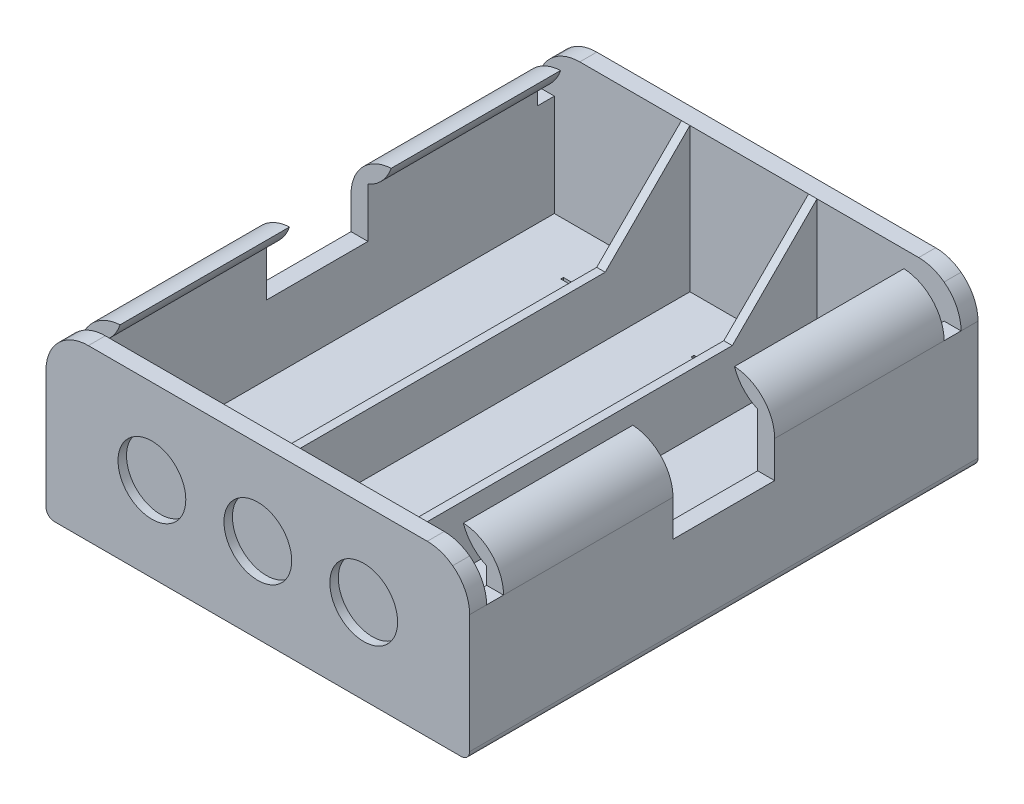
SolidWorks part; units mm, degrees
ref_plane "Plan de face" through (0, 0, 0) normal (0, 0, 1) x (1, 0, 0)
ref_plane "Plan de dessus" through (0, 0, 0) normal (0, 1, 0) x (1, 0, 0)
ref_plane "Plan de droite" through (0, 0, 0) normal (1, 0, 0) x (0, 0, -1)
sketch "Esquisse1" plane through (0, 0, 0) normal (0, 0, 1) x (1, 0, 0)
  line L1 (0, 0) -> (-50, 0)
  line L2 (0, 0) -> (0, 17)
  line L3 (0, 17) -> (-50, 17)
  line L4 (-50, 0) -> (-50, 17)
  dimension "D1" = 50
  dimension "D2" = 17
extrude "Boss.-Extru.1" add sketch "Esquisse1" along normal blind 60
sketch "Esquisse2" plane through (0, 17, 0) normal (0, 1, 0) x (1, 0, 0)
  line L0 (0, -60) -> (-50, -60) construction
  line L1 (-2, -58) -> (-48, -58)
  line L2 (-2, -58) -> (-2, -2)
  line L3 (-2, -2) -> (-48, -2)
  line L4 (-48, -58) -> (-48, -2)
  line L5 (-50, -60) -> (-50, 0) construction
  line L6 (0, -60) -> (0, 0) construction
  line L7 (0, 0) -> (-50, 0) construction
  dimension "D1" = 2
  dimension "D2" = 2
  dimension "D3" = 2
  dimension "D4" = 2
extrude "Enlèv. mat.-Extru.1" cut sketch "Esquisse2" against normal blind 14
sketch "Esquisse3" plane through (0, 17, 0) normal (0, 1, 0) x (1, 0, 0)
  line L0 (0, 0) -> (-50, 0) construction
  line L1 (0, -60) -> (-5, -60)
  line L2 (0, -60) -> (0, 0)
  line L3 (0, 0) -> (-5, 0)
  line L4 (-5, -60) -> (-5, 0)
  line L6 (-50, -60) -> (-45, -60)
  line L7 (-50, -60) -> (-50, 0)
  line L8 (-50, 0) -> (-45, 0)
  line L9 (-45, -60) -> (-45, 0)
  dimension "D1" = 5
  dimension "D2" = 5
extrude "Boss.-Extru.2" add sketch "Esquisse3" along normal blind 3
fillet "Congé4" radius 5 2 edges at (-50, 20, 30) (0, 20, 30)
fillet "Congé5" radius 5 2 edges at (-45, 17, 30) (-5, 17, 30)
sketch "Esquisse4" plane through (0, 0, 0) normal (1, 0, 0) x (0, 0, -1)
  line L0 (-30, 0) -> (-30, 21.3993)
  line L1 (-60, 0) -> (0, 0) construction
  line L3 (-30, 10.6996) -> (-36, 10.6996)
  line L4 (-30, 10.6996) -> (-30, 21.3993)
  line L5 (-30, 21.3993) -> (-36, 21.3993)
  line L6 (-36, 10.6996) -> (-36, 21.3993)
  line L7 (-30, 10.6996) -> (-24, 10.6996)
  line L8 (-30, 10.6996) -> (-30, 21.3993)
  line L9 (-30, 21.3993) -> (-24, 21.3993)
  line L10 (-24, 10.6996) -> (-24, 21.3993)
  line M4 (0, 15) -> (-60, 15)
  dimension "D1" = 6
  dimension "D2" = 6
extrude "Enlèv. mat.-Extru.2" cut sketch "Esquisse4" against normal blind 13 contours L10 L9 L0 M4 | L7 L10 L0 M4 | L6 L3 L0 M4 | L6 L0 L5 M4
sketch "Esquisse5" plane through (-50, 0, 0) normal (-1, 0, 0) x (0, 0, 1)
  line L0 (30, 0) -> (30, 22.2931)
  line L1 (60, 0) -> (0, 0) construction
  line L3 (30, 11.1466) -> (24, 11.1466)
  line L4 (30, 11.1466) -> (30, 21.3972)
  line L5 (30, 21.3972) -> (24, 21.3972)
  line L6 (24, 11.1466) -> (24, 21.3972)
  line L7 (30, 11.1466) -> (36, 11.1466)
  line L8 (30, 11.1466) -> (30, 21.3972)
  line L9 (30, 21.3972) -> (36, 21.3972)
  line L10 (36, 11.1466) -> (36, 21.3972)
  line M4 (60, 15) -> (0, 15)
  dimension "D1" = 6
  dimension "D2" = 6
extrude "Enlèv. mat.-Extru.3" cut sketch "Esquisse5" against normal blind 13 contours L6 L3 L0 M4 | L7 L10 L0 M4 | L10 L9 L0 M4 | L6 L0 L5 M4
sketch "Esquisse6" plane through (0, 17, 0) normal (0, 1, 0) x (1, 0, 0)
  line L1 (-2, 0) -> (-48, 0)
  line L2 (-2, 0) -> (-2, -2)
  line L3 (-2, -2) -> (-48, -2)
  line L4 (-48, 0) -> (-48, -2)
  line L5 (-48, -60) -> (-2, -60)
  line L6 (-48, -60) -> (-48, -58)
  line L7 (-48, -58) -> (-2, -58)
  line L8 (-2, -60) -> (-2, -58)
extrude "Boss.-Extru.3" add sketch "Esquisse6" along normal blind 3
fillet "Congé6" radius 5 1 edges at (-2, 20, 1)
fillet "Congé7" radius 5 1 edges at (-48, 20, 1)
fillet "Congé8" radius 5 2 edges at (-2, 20, 59) (-48, 20, 59)
sketch "Esquisse7" plane through (-50, 0, 0) normal (-1, 0, 0) x (0, 0, 1)
  line L0 (0, 0) -> (4, 0)
  line L1 (60, 0) -> (0, 0) construction
  line L2 (24, 15) -> (0, 15) construction
  line L3 (4, 0) -> (2, 0)
  line L4 (4, 0) -> (4, 20.2103)
  line L5 (4, 20.2103) -> (2, 20.2103)
  line L6 (2, 0) -> (2, 20.2103)
  line L7 (2, 20.2103) -> (4, 20.2103)
  line L8 (2, 20.2103) -> (2, 15)
  line L9 (2, 15) -> (4, 15)
  line L10 (4, 20.2103) -> (4, 15)
  line M4 (24, 15) -> (0, 15)
  dimension "D1" = 4
  dimension "D2" = 2
extrude "Enlèv. mat.-Extru.4" cut sketch "Esquisse7" against normal blind 62 contours L6 L4 L5 M4
sketch "Esquisse8" plane through (-50, 0, 0) normal (-1, 0, 0) x (0, 0, 1)
  line L0 (60, 0) -> (56, 0)
  line L1 (60, 0) -> (0, 0) construction
  line L2 (60, 15) -> (36, 15) construction
  line L3 (56, 0) -> (58, 0)
  line L4 (56, 0) -> (56, 23.2572)
  line L5 (56, 23.2572) -> (58, 23.2572)
  line L6 (58, 0) -> (58, 23.2572)
  line L7 (56, 23.2572) -> (58, 23.2572)
  line L8 (56, 23.2572) -> (56, 15)
  line L9 (56, 15) -> (58, 15)
  line L10 (58, 23.2572) -> (58, 15)
  line M10 (60, 15) -> (36, 15)
  dimension "D1" = 4
  dimension "D2" = 2
extrude "Enlèv. mat.-Extru.5" cut sketch "Esquisse8" against normal blind 62 contours L6 L5 L4 M10
sketch "Esquisse9" plane through (0, 3, 0) normal (0, 1, 0) x (1, 0, 0)
  line L0 (-2, -58) -> (-17, -58)
  line L1 (-48, -58) -> (-2, -58) construction
  line L2 (-48, -58) -> (-33, -58)
  line L3 (-17, -58) -> (-33, -58)
  line L4 (-2, -2) -> (-48, -2) construction
  line L5 (-17, -58) -> (-18, -58)
  line L6 (-17, -58) -> (-17, -2)
  line L7 (-17, -2) -> (-18, -2)
  line L8 (-18, -58) -> (-18, -2)
  line L10 (-33, -58) -> (-32, -58)
  line L11 (-33, -58) -> (-33, -2)
  line L12 (-33, -2) -> (-32, -2)
  line L13 (-32, -58) -> (-32, -2)
  dimension "D1" = 15
  dimension "D2" = 15
  dimension "D3" = 1
  dimension "D4" = 1
extrude "Boss.-Extru.4" add sketch "Esquisse9" along normal blind 7 contours L10 L13 L12 L11 | L5 L8 L7 L6
sketch "Esquisse13" plane through (-17, 0, 0) normal (1, 0, 0) x (0, 0, -1)
  line L0 (-58, 10) -> (-48, 10)
  line L1 (-58, 10) -> (-2, 10) construction
  line L2 (-48, 10) -> (-58, 20)
  line L3 (-58, 10) -> (-58, 20)
  dimension "D1" = 10
extrude "Boss.-Extru.5" add sketch "Esquisse13" against normal blind 1
sketch "Esquisse15" plane through (-32, 0, 0) normal (1, 0, 0) x (0, 0, -1)
  line L0 (-58, 10) -> (-48, 10)
  line L1 (-58, 10) -> (-2, 10) construction
  line L2 (-48, 10) -> (-58, 20)
  line L3 (-58, 20) -> (-58, 10)
  dimension "D1" = 10
extrude "Boss.-Extru.6" add sketch "Esquisse15" against normal blind 1
sketch "Esquisse16" plane through (-32, 0, 0) normal (1, 0, 0) x (0, 0, -1)
  line L0 (-2, 10) -> (-12.0005, 10)
  line L1 (-48, 10) -> (-2, 10) construction
  line L2 (-12.0005, 10) -> (-2, 20.0005)
  line L3 (-2, 20.0005) -> (-2, 10)
extrude "Boss.-Extru.7" add sketch "Esquisse16" against normal blind 1
sketch "Esquisse17" plane through (-17, 0, 0) normal (1, 0, 0) x (0, 0, -1)
  line L0 (-2, 10) -> (-12, 10)
  line L1 (-48, 10) -> (-2, 10) construction
  line L2 (-12, 10) -> (-2, 20)
  line L3 (-2, 20) -> (-2, 10)
  dimension "D1" = 10
extrude "Boss.-Extru.8" add sketch "Esquisse17" against normal blind 1
sketch "Esquisse18" plane through (0, 3, 0) normal (0, 1, 0) x (1, 0, 0)
  text T0 "+\r\n"
  text T1 "+"
  text T2 "+\r\n"
extrude "Enlèv. mat.-Extru.6" cut sketch "Esquisse18" against normal blind 0.5
sketch "Esquisse19" plane through (0, 3, 0) normal (0, 1, 0) x (1, 0, 0)
  text T0 "-\r\n"
  text T1 "-\r\n"
  text T2 "-\r\n"
extrude "Enlèv. mat.-Extru.7" cut sketch "Esquisse19" against normal blind 0.5
fillet "Congé9" radius 1 1 edges at (0, 0, 30)
fillet "Congé10" radius 1 1 edges at (-50, 0, 30)
sketch "Esquisse20" plane through (0, 0, 0) normal (0, 0, -1) x (-1, 0, 0)
  line L0 (0, 0) -> (50, 0)
  line L1 (25, 0) -> (0, 0)
  line L2 (25, 0) -> (50, 0)
  line L3 (12.5, 0) -> (12.5, 20)
  line L4 (5, 20) -> (45, 20) construction
  line L5 (25, 0) -> (25, 20)
  line L6 (50, 0) -> (25, 0)
  line L7 (37.5, 0) -> (37.5, 20)
  circle A0 centre (12.5, 10) radius 4
  circle A1 centre (25, 10) radius 4
  circle A2 centre (37.5, 10) radius 4
extrude "Enlèv. mat.-Extru.8" cut sketch "Esquisse20" against normal blind 1 contours L3 A0 | L3 A0 | L5 A1 | L5 A1 | L7 A2 | L7 A2
sketch "Esquisse21" plane through (0, 0, 60) normal (0, 0, 1) x (1, 0, 0)
  line L0 (0, 0) -> (-50, 0)
  line L1 (-50, 0) -> (-25, 0)
  line L2 (-25, 0) -> (0, 0)
  line L3 (-37.5, 0) -> (-37.5, 20)
  line L4 (-45, 20) -> (-5, 20) construction
  line L5 (-25, 0) -> (-25, 20)
  line L6 (-25, 0) -> (0, 0)
  line L7 (-12.5, 0) -> (-12.5, 20)
  circle A0 centre (-37.5, 10) radius 4
  circle A1 centre (-25, 10) radius 4
  circle A2 centre (-12.5, 10) radius 4
extrude "Enlèv. mat.-Extru.9" cut sketch "Esquisse21" against normal blind 1 contours L3 A0 | L3 A0 | L5 A1 | L5 A1 | L7 A2 | L7 A2
sketch "Esquisse22" plane through (0, 0, 1) normal (0, 0, -1) x (-1, 0, 0)
  line L1 (11.75, 5.7234) -> (13.25, 5.7234)
  line L2 (11.75, 5.7234) -> (11.75, 4.0234)
  line L3 (11.75, 4.0234) -> (13.25, 4.0234)
  line L4 (13.25, 5.7234) -> (13.25, 4.0234)
  line L5 (24.25, 5.7302) -> (25.75, 5.7302)
  line L6 (24.25, 5.7302) -> (24.25, 4.0302)
  line L7 (24.25, 4.0302) -> (25.75, 4.0302)
  line L8 (25.75, 5.7302) -> (25.75, 4.0302)
  circle A0 centre (25, 10) radius 4 construction
  circle A1 centre (12.5, 10) radius 4 construction
  dimension "D1" = 1.5
  dimension "D2" = 1.7
  dimension "D3" = 1.5
  dimension "D4" = 1.7
  dimension "D5" = 0.75
  dimension "D6" = 0.75
extrude "Boss.-Extru.9" add sketch "Esquisse22" along normal blind 9
